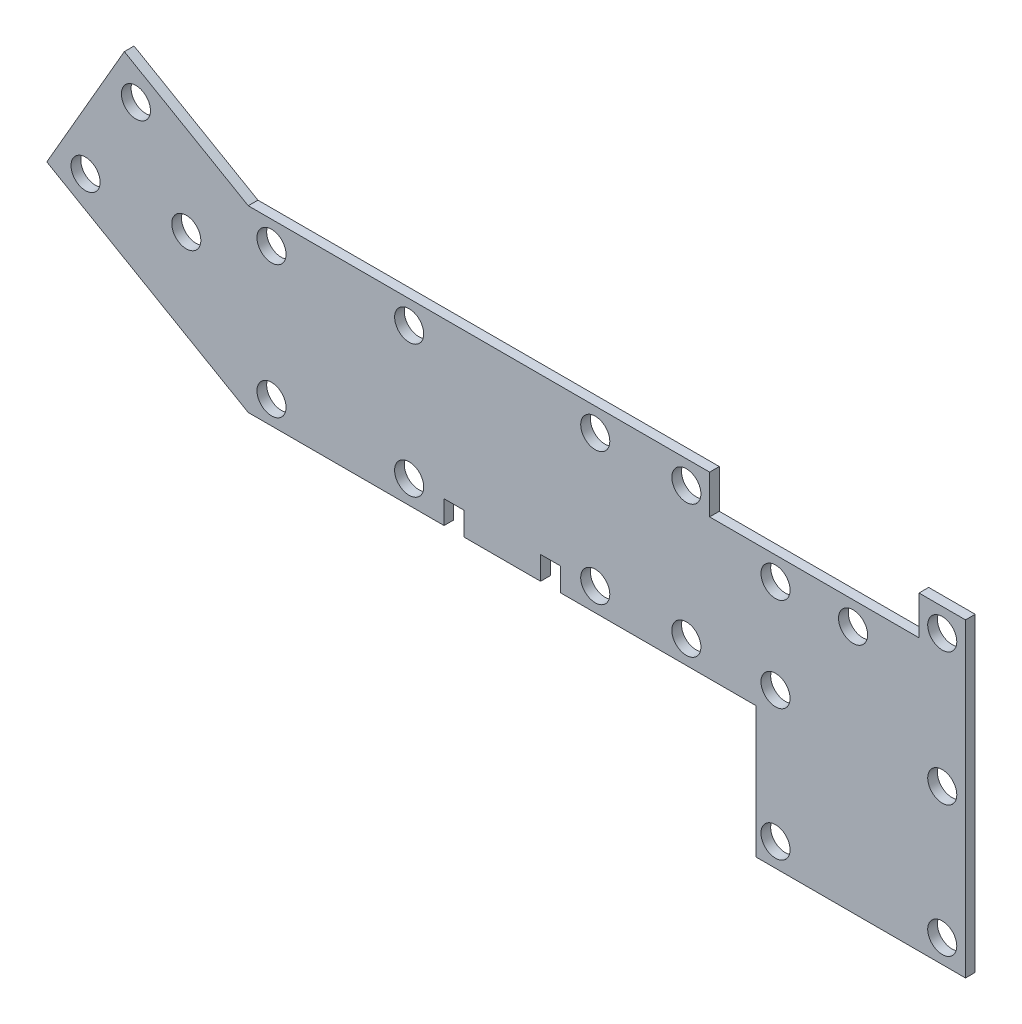
SolidWorks part; units mm, degrees
material "1023 Carbon Steel Sheet (SS)"
ref_plane "Front Plane" through (0, 0, 0) normal (0, 0, 1) x (1, 0, 0)
ref_plane "Top Plane" through (0, 0, 0) normal (0, 1, 0) x (1, 0, 0)
ref_plane "Right Plane" through (0, 0, 0) normal (1, 0, 0) x (0, 0, -1)
sketch "Sketch1" plane through (0, 0, 0) normal (0, 0, 1) x (1, 0, 0)
  line L0 (0, 0) -> (-40.5911, 23.4353)
  line L1 (-40.5911, 23.4353) -> (-65.9911, -20.5588)
  line L2 (-65.9911, -20.5588) -> (0, -58.6588)
  line L3 (0, -58.6588) -> (64.135, -58.6588)
  line L4 (64.135, -58.6588) -> (64.135, -51.0388)
  line L5 (64.135, -51.0388) -> (70.612, -51.0388)
  line L6 (70.612, -51.0388) -> (70.612, -58.6588)
  line L7 (70.612, -58.6588) -> (95.758, -58.6588)
  line L8 (95.758, -58.6588) -> (95.758, -51.0388)
  line L9 (95.758, -51.0388) -> (102.235, -51.0388)
  line L10 (102.235, -51.0388) -> (102.235, -58.6588)
  line L11 (102.235, -58.6588) -> (166.37, -58.6588)
  line L12 (166.37, -58.6588) -> (166.37, -101.6)
  line L13 (166.37, -101.6) -> (234.95, -101.6)
  line L14 (234.95, -101.6) -> (234.95, 0)
  line L15 (234.95, 0) -> (219.71, 0)
  line L16 (219.71, 0) -> (219.71, -12.7)
  line L17 (219.71, -12.7) -> (151.13, -12.7)
  line L18 (151.13, -12.7) -> (151.13, 0)
  line L19 (151.13, 0) -> (113.03, 0)
  line L23 (113.03, 0) -> (0, 0)
  circle A1 centre (-20.2956, -17.6117) radius 4.7625
  circle A2 centre (-53.2911, -17.6117) radius 4.7625
  circle A3 centre (-36.7934, 10.9633) radius 4.7625
  circle A4 centre (-36.7934, -8.0867) radius 19.05 construction
  circle A5 centre (7.62, -51.0388) radius 4.7625
  circle A6 centre (7.62, -7.62) radius 4.7625
  circle A7 centre (52.705, -7.62) radius 4.7625
  circle A8 centre (113.665, -7.62) radius 4.7625
  circle A9 centre (143.51, -7.62) radius 4.7625
  circle A10 centre (113.665, -51.0388) radius 4.7625
  circle A11 centre (52.705, -51.0388) radius 4.7625
  circle A12 centre (143.51, -51.0388) radius 4.7625
  circle A13 centre (172.72, -20.32) radius 4.7625
  circle A14 centre (198.12, -20.32) radius 4.7625
  circle A15 centre (227.33, -7.62) radius 4.7625
  circle A16 centre (227.33, -93.98) radius 4.7625
  circle A17 centre (172.72, -93.98) radius 4.7625
  circle A18 centre (227.33, -51.0388) radius 4.7625
  circle A19 centre (172.72, -51.0388) radius 4.7625
  point P3 (-36.7934, -8.0867)
  point P24 (185.42, -12.7)
  point P28 (-53.2911, 1.4383)
  point P33 (83.185, -58.6588)
  dimension "D18" = 9.525
  dimension "D21" = 3
  dimension "D16" = 38.1
  dimension "D17" = 7.62
  dimension "D1" = 30
  dimension "D2" = 76.2
  dimension "D3" = 50.8
  dimension "D4" = 83.185
  dimension "D5" = 68.58
  dimension "D6" = 38.1
  dimension "D8" = 25.146
  dimension "D9" = 166.37
  dimension "D10" = 7.62
  dimension "D11" = 19.05
  dimension "D12" = 38.1
  dimension "D13" = 101.6
  dimension "D14" = 15.24
  dimension "D15" = 12.7
  dimension "D19" = 19.05
  dimension "D20" = 25.4
  dimension "D22" = 7.62
  dimension "D23" = 7.62
  dimension "D24" = 30.48
  dimension "D25" = 30.48
  dimension "D26" = 7.62
  dimension "D27" = 7.62
  dimension "D28" = 12.7
  dimension "D29" = 12.7
  dimension "D30" = 7.62
  dimension "D31" = 7.62
  dimension "D32" = 7.62
extrude "Boss-Extrude1" add sketch "Sketch1" along normal blind 3.175 contours L19 L23 L0 L1 L2 L3 L4 L5 L6 L7 L8 L9 L10 L11 L12 L13 L14 L15 L16 L17 L18 A19 A18 A17 A16 A15 A14 A13 A12 A11 A10 A9 A8 A7 A6 A5 region at (103.3129, -36.1726, 0)
